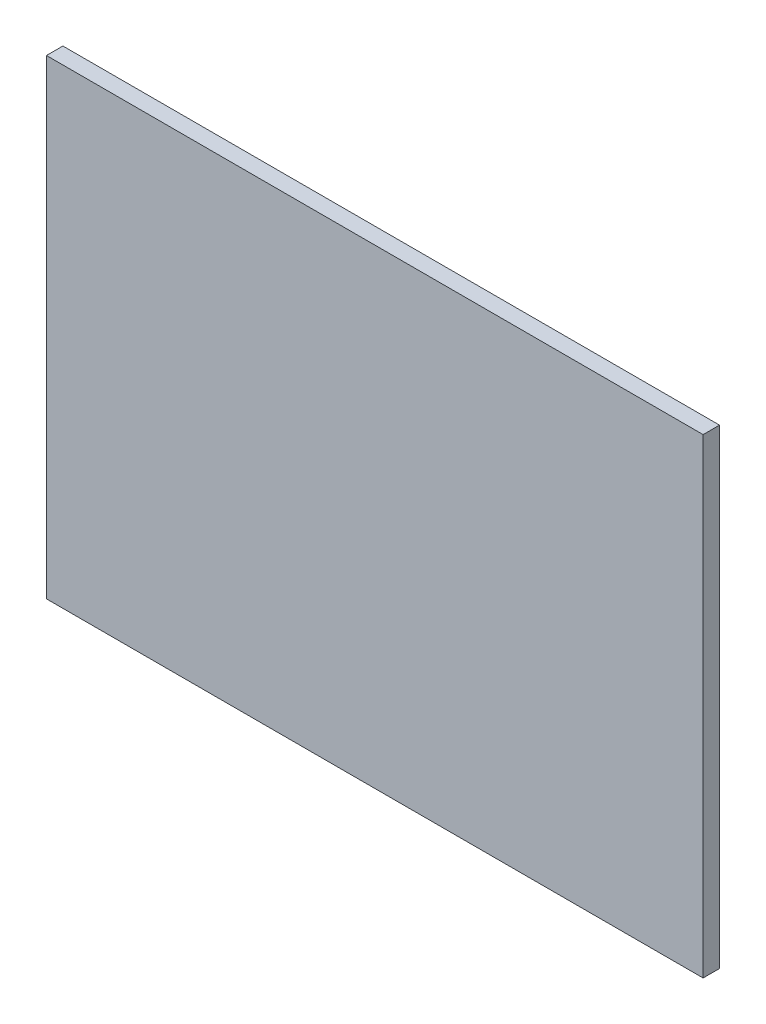
SolidWorks part; units mm, degrees
ref_plane "Alzado" through (0, 0, 0) normal (0, 0, 1) x (1, 0, 0)
ref_plane "Planta" through (0, 0, 0) normal (0, 1, 0) x (1, 0, 0)
ref_plane "Vista lateral" through (0, 0, 0) normal (1, 0, 0) x (0, 0, -1)
sketch "Croquis1" plane through (0, 0, 0) normal (0, 0, 1) x (1, 0, 0)
  line L1 (-300, 215) -> (300, 215)
  line L2 (-300, 215) -> (-300, -215)
  line L3 (-300, -215) -> (300, -215)
  line L4 (300, 215) -> (300, -215)
  line L5 (-300, 215) -> (300, -215) construction
  line L6 (-300, -215) -> (300, 215) construction
  point P0 (0, 0)
  dimension "D1" = 430
  dimension "D2" = 600
extrude "Saliente-Extruir1" add sketch "Croquis1" along normal blind 15
